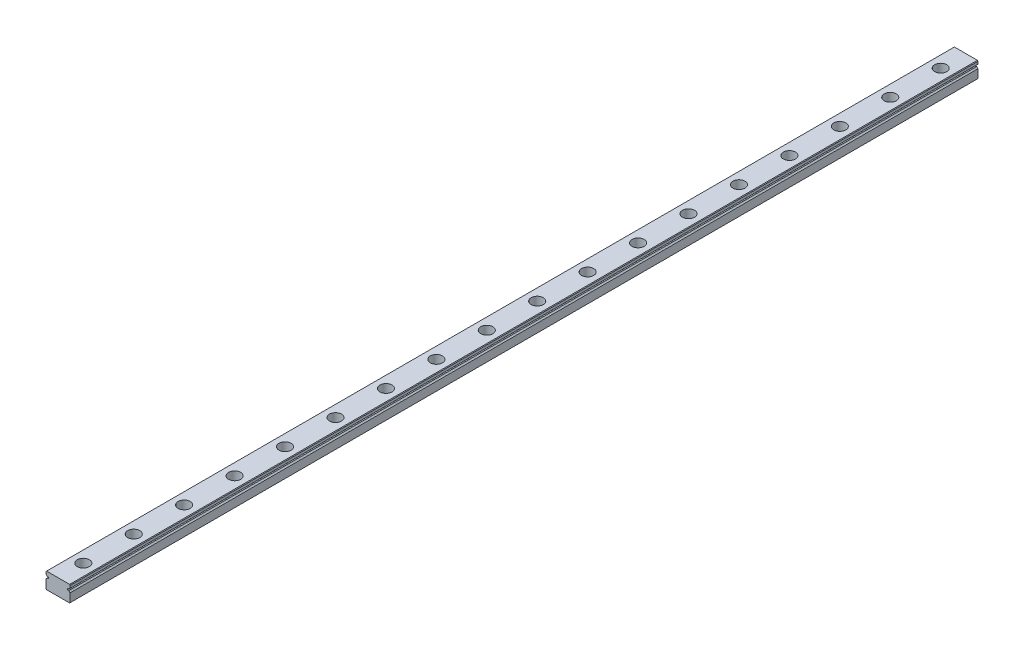
SolidWorks part; units mm, degrees
ref_plane "Спереди" through (0, 0, 0) normal (0, 0, 1) x (1, 0, 0)
ref_plane "Сверху" through (0, 0, 0) normal (0, 1, 0) x (1, 0, 0)
ref_plane "Справа" through (0, 0, 0) normal (1, 0, 0) x (0, 0, -1)
sketch "Эскиз1" plane through (0, 0, 0) normal (0, 0, 1) x (1, 0, 0)
  line L0 (-6, 3.7) -> (-5.7, 4)
  line L1 (-5.7, -4) -> (5.7, -4)
  line L2 (-6, -3.7) -> (-6, 0.549)
  line L3 (-5.7, 4) -> (5.7, 4)
  line L4 (6, -3.7) -> (6, 0.549)
  line L5 (-6, -4) -> (6, 4) construction
  line L6 (-6, 4) -> (6, -4) construction
  line L7 (-6, -3.7) -> (-5.7, -4)
  line L8 (5.7, -4) -> (6, -3.7)
  line L9 (5.7, 4) -> (6, 3.7)
  line L10 (-6, 2.451) -> (-6, 3.7)
  line L11 (-5.3546, 1.7981) -> (-4.6435, 1.7981)
  line L12 (0, 5.4188) -> (0, -5.747) construction
  line L13 (-5.3546, 1.2019) -> (-4.6435, 1.2019)
  line L14 (-4.6435, 1.7981) -> (-4.6435, 1.2019)
  line L15 (4.6435, 1.7981) -> (4.6435, 1.2019)
  line L16 (5.3546, 1.2019) -> (4.6435, 1.2019)
  line L17 (5.3546, 1.7981) -> (4.6435, 1.7981)
  line L18 (6, 2.451) -> (6, 3.7)
  line L19 (4.6435, 1.7981) -> (5.3546, 1.7981) construction
  arc A0 (-6, 0.549) -> (-5.3546, 1.2019) centre (-6.3091, 1.5) ccw
  arc A1 (-5.3546, 1.7981) -> (-6, 2.451) centre (-6.3091, 1.5) ccw
  arc A2 (5.3546, 1.7981) -> (6, 2.451) centre (6.3091, 1.5) cw
  arc A3 (6, 0.549) -> (5.3546, 1.2019) centre (6.3091, 1.5) cw
  point P0 (0, 0)
extrude "Бобышка-Вытянуть1" add sketch "Эскиз1" along normal blind 450
sketch "Эскиз2" plane through (0, 4, 0) normal (0, 1, 0) x (1, 0, 0)
  line L0 (0, 0) -> (0, -26.2396) construction
  line L1 (5.7, 0) -> (-5.7, 0) construction
  line L2 (-3.8306, -12.5) -> (3.8306, -12.5) construction
  circle A0 centre (0, -12.5) radius 3
  circle A1 centre (0, -12.5) radius 1.75
  dimension "D2" = 3.5
  dimension "D3" = 6
  dimension "D1" = 12.5
extrude "Вырез-Вытянуть1" cut sketch "Эскиз2" against normal blind 4.5
extrude "Вырез-Вытянуть2" cut sketch "Эскиз2<2>" against normal through all contours A1 region at (0, 4, 12.5)
sketch "Эскиз2<2>" plane through (0, 4, 0) normal (0, 1, 0) x (1, 0, 0) same geometry as "Эскиз2"
pattern_linear "Линейный массив1" count 18 spacing 25 along (0, 0, 1) of "Вырез-Вытянуть1", "Вырез-Вытянуть2"
